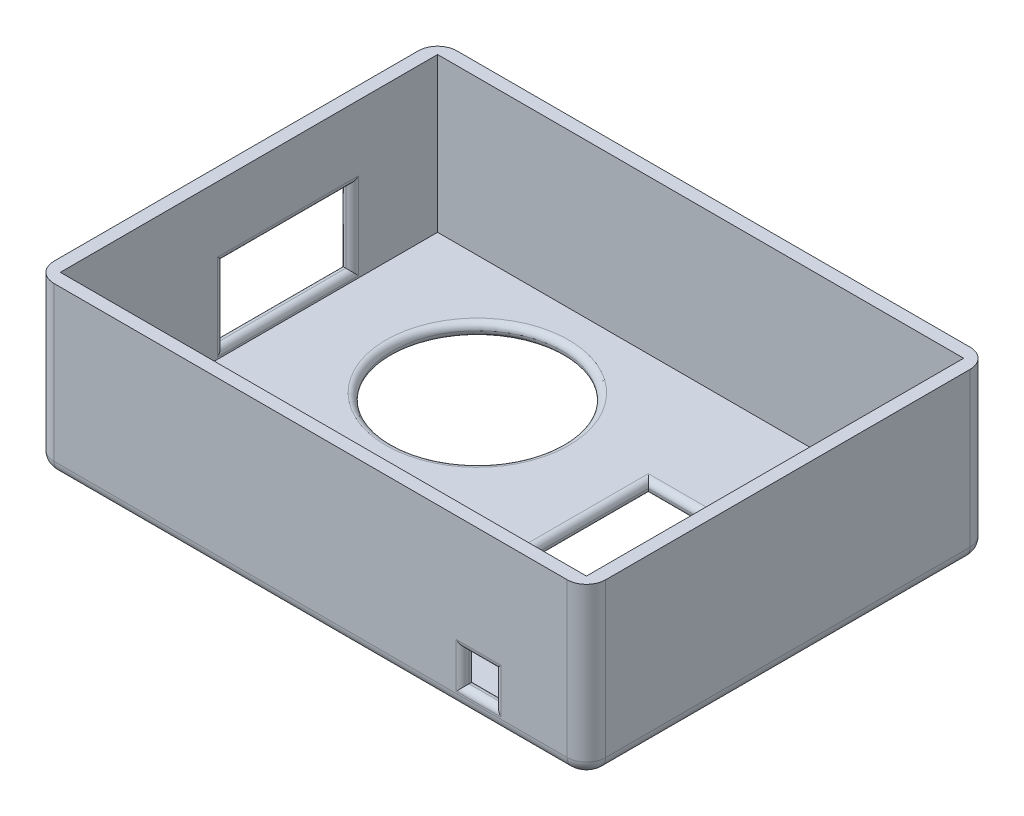
SolidWorks part; units mm, degrees
ref_plane "Front Plane" through (0, 0, 0) normal (0, 0, 1) x (1, 0, 0)
ref_plane "Top Plane" through (0, 0, 0) normal (0, 1, 0) x (1, 0, 0)
ref_plane "Right Plane" through (0, 0, 0) normal (1, 0, 0) x (0, 0, -1)
sketch "Sketch1" plane through (0, 0, 0) normal (0, 1, 0) x (1, 0, 0)
  line L1 (33.232, -29) -> (-48.768, -29)
  line L2 (33.232, -29) -> (33.232, 29.798)
  line L3 (33.232, 29.798) -> (-48.768, 29.798)
  line L4 (-48.768, -29) -> (-48.768, 29.798)
  line L5 (-50.768, -31) -> (35.232, -31)
  line L6 (-50.768, -31) -> (-50.768, 31.798)
  line L7 (-50.768, 31.798) -> (35.232, 31.798)
  line L8 (35.232, -31) -> (35.232, 31.798)
  line L9 (1.232, 12.648) -> (18.732, 12.648)
  line L10 (1.232, 12.648) -> (1.232, -23)
  line L11 (1.232, -23) -> (18.732, -23)
  line L12 (18.732, 12.648) -> (18.732, -23)
  line L13 (-50.768, 31.798) -> (35.232, 31.798)
  line L14 (-50.768, 31.798) -> (-50.768, -31)
  line L15 (-50.768, -31) -> (35.232, -31)
  line L16 (35.232, 31.798) -> (35.232, -31)
  line L17 (-48.768, 29.798) -> (33.232, 29.798)
  line L18 (-48.768, 29.798) -> (-48.768, -29)
  line L19 (-48.768, -29) -> (33.232, -29)
  line L20 (33.232, 29.798) -> (33.232, -29)
  circle A1 centre (-24.017, 11.249) radius 13.249
  point P0 (0, 0)
  point P6 (0, 0)
  point P11 (9.882, 11.072)
  point P18 (9.982, 12.648)
  dimension "D8" = 14.5
  dimension "D1" = 82
  dimension "D2" = 2
  dimension "D3" = 2
  dimension "D4" = 2
  dimension "D5" = 2
  dimension "D6" = 6
  dimension "D7" = 17.5
  dimension "D9" = 17.15
extrude "Boss-Extrude6" add sketch "Sketch1" along normal blind 2 contours L4 L1 L2 L3 A1 L9 L12 L11 L10 region at (-8.3474, 0, 0.2882)
sketch "Sketch3" plane through (0, 0, 0) normal (0, 1, 0) x (1, 0, 0)
  line L1 (-50.768, 31.798) -> (35.232, 31.798)
  line L2 (-50.768, 31.798) -> (-50.768, -31)
  line L3 (-50.768, -31) -> (35.232, -31)
  line L4 (35.232, 31.798) -> (35.232, -31)
  line L5 (-48.768, 29.798) -> (33.232, 29.798)
  line L6 (-48.768, 29.798) -> (-48.768, -29)
  line L7 (-48.768, -29) -> (33.232, -29)
  line L8 (33.232, 29.798) -> (33.232, -29)
  dimension "D1" = 2
  dimension "D2" = 2
  dimension "D3" = 2
  dimension "D4" = 2
extrude "Boss-Extrude7" add sketch "Sketch3" along normal blind 26
fillet "Fillet1" radius 3 4 edges at (-50.768, 13, 31) (35.232, 13, 31) (35.232, 13, -31.798) (-50.768, 13, -31.798)
fillet "Fillet2" radius 2 8 edges at (34.3533, 0, 30.1213) (-49.8893, 0, 30.1213) (-49.8893, 0, -30.9193) (34.3533, 0, -30.9193) (-7.768, 0, -31.798) (-50.768, 0, -0.399) (-7.768, 0, 31) (35.232, 0, -0.399)
fillet "Fillet3" radius 1 8 edges at (9.982, 0, -12.648) (9.982, 2, -12.648) (18.732, 2, 5.176) (18.732, 0, 5.176) (9.982, 2, 23) (9.982, 0, 23) (1.232, 2, 5.176) (1.232, 0, 5.176)
fillet "Fillet4" radius 1 2 edges at (-24.017, 2, 2) (-24.017, 0, 2)
sketch "Sketch5" plane through (0, 0, 31) normal (0, 0, 1) x (1, 0, 0)
  line L0 (-47.768, 2) -> (32.232, 2) construction
  line L1 (15.932, 8.3) -> (20.932, 8.3)
  line L2 (15.932, 8.3) -> (15.932, 3.3)
  line L3 (15.932, 3.3) -> (20.932, 3.3)
  line L4 (20.932, 8.3) -> (20.932, 3.3)
  line L5 (32.232, 2) -> (32.232, 26) construction
  dimension "D1" = 1.3
  dimension "D2" = 5
  dimension "D3" = 11.3
  dimension "D4" = 5
extrude "Cut-Extrude1" cut sketch "Sketch5" against normal blind 26
sketch "Sketch7" plane through (-50.768, 0, 0) normal (-1, 0, 0) x (0, 0, 1)
  line L0 (-28.798, 2) -> (28, 2) construction
  line L6 (-16.498, 14.8) -> (3.502, 14.8)
  line L8 (-16.498, 14.8) -> (-16.498, 3.3)
  line L9 (-16.498, 3.3) -> (3.502, 3.3)
  line L10 (3.502, 14.8) -> (3.502, 3.3)
  line L11 (-28.798, 26) -> (-28.798, 2) construction
  dimension "D3" = 11.5
  dimension "D1" = 1.3
  dimension "D2" = 12.3
  dimension "D4" = 20
extrude "Cut-Extrude2" cut sketch "Sketch7" against normal blind 26
fillet "Fillet5" radius 1 8 edges at (-50.768, 9.05, -16.498) (-48.768, 9.05, -16.498) (-50.768, 3.3, -6.498) (-48.768, 3.3, -6.498) (-48.768, 9.05, 3.502) (-50.768, 9.05, 3.502) (-48.768, 14.8, -6.498) (-50.768, 14.8, -6.498)
fillet "Fillet6" radius 1 8 edges at (15.932, 5.8, 31) (15.932, 5.8, 29) (18.432, 3.3, 31) (18.432, 3.3, 29) (20.932, 5.8, 29) (20.932, 5.8, 31) (18.432, 8.3, 29) (18.432, 8.3, 31)
